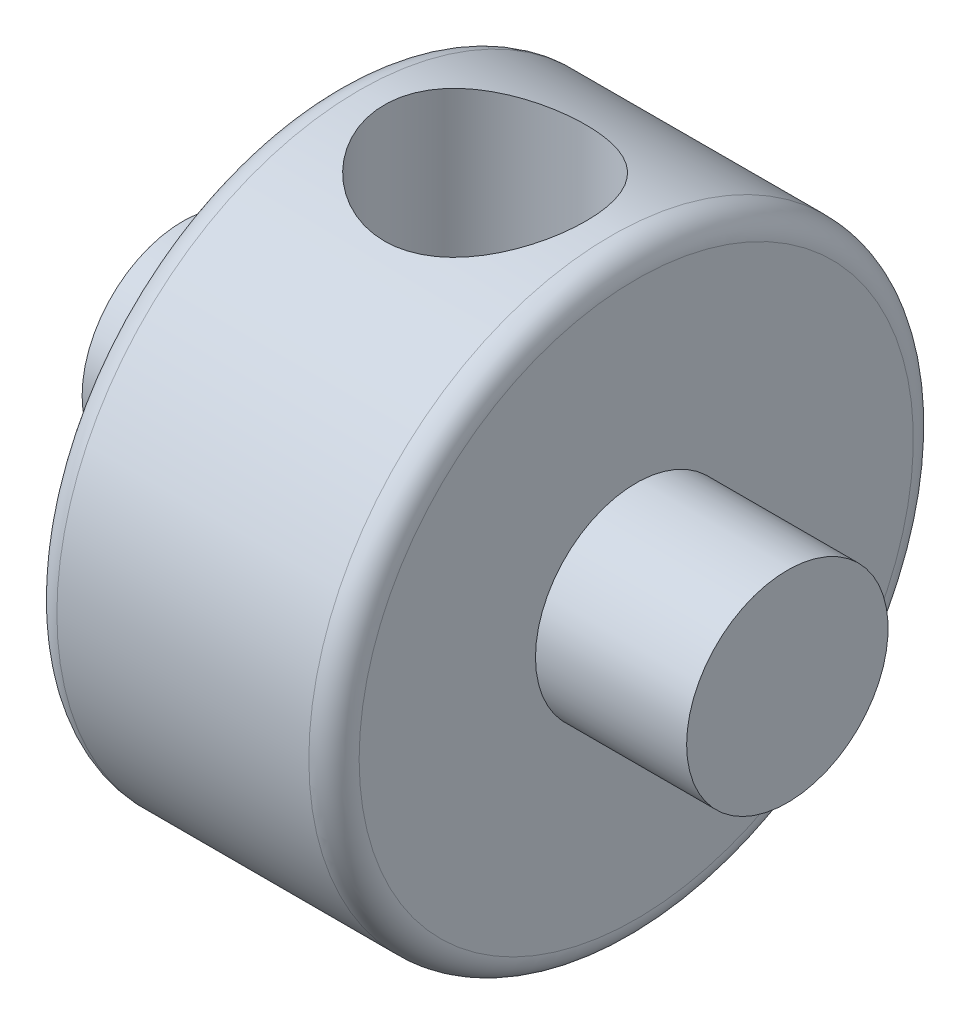
SolidWorks part; units mm, degrees
material "Alloy Steel"
ref_plane "Front Plane" through (0, 0, 0) normal (0, 0, 1) x (1, 0, 0)
ref_plane "Top Plane" through (0, 0, 0) normal (0, 1, 0) x (1, 0, 0)
ref_plane "Right Plane" through (0, 0, 0) normal (1, 0, 0) x (0, 0, -1)
sketch "Sketch1" plane through (0, 0, 0) normal (0, 0, 1) x (1, 0, 0)
  line L0 (-9.525, 0) -> (-9.525, 3.175)
  line L1 (-9.525, 3.175) -> (-4.7625, 3.175)
  line L2 (-4.7625, 3.175) -> (-4.7625, 9.525)
  line L3 (-4.7625, 9.525) -> (4.7625, 9.525)
  line L4 (4.7625, 9.525) -> (4.7625, 3.175)
  line L5 (4.7625, 3.175) -> (9.525, 3.175)
  line L6 (9.525, 3.175) -> (9.525, 0)
  line L7 (9.525, 0) -> (-9.525, 0)
  line L8 (-58.3897, 0) -> (112.59, 0) construction
  dimension "D1" = 19.05
  dimension "D2" = 4.7625
  dimension "D3" = 19.05
  dimension "D4" = 6.35
revolve "Revolve1" add sketch "Sketch1" angle 360 about L8
fillet "Fillet1" radius 0.7925 2 edges at (-4.7625, 0, 9.525) (4.7625, 0, 9.525)
hole_wizard "#97 (0.0059) Diameter Hole1" positions "3DSketch1" profile "Sketch2" hole size "#97" standard "Ansi Inch" end condition through all
sketch3d "3DSketch1"
  point P0 (0, 9.525, 0)
sketch "Sketch2" plane through (0, 9.525, 0) normal (1, 0, 0) x (0, 0, 1)
  line L0 (0, 0) -> (0, 19.05)
  line L1 (0, 19.05) -> (3.175, 19.05)
  line L2 (3.175, 19.05) -> (3.175, 0)
  line L5 (3.175, 0) -> (0, 0)
  line L11 (0, -6.35) -> (0, 107.95) construction
  dimension "Thru Hole Dia." = 6.35
  dimension "Thru Hole Depth" = 19.05
